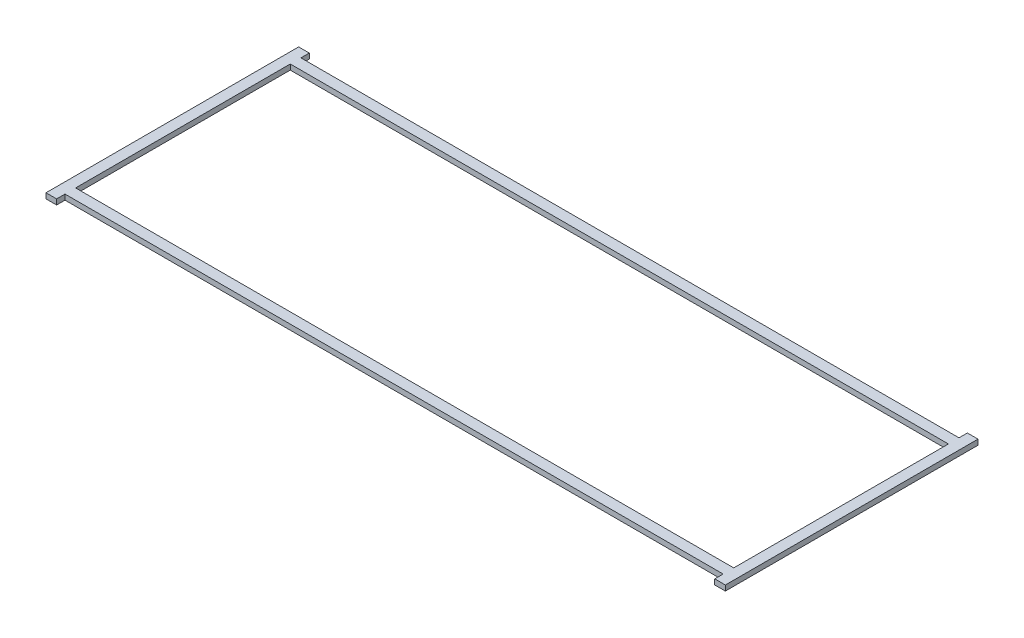
SolidWorks part; units mm, degrees
ref_plane "Front" through (0, 0, 0) normal (0, 0, 1) x (1, 0, 0)
ref_plane "Top" through (0, 0, 0) normal (0, 1, 0) x (1, 0, 0)
ref_plane "Right" through (0, 0, 0) normal (1, 0, 0) x (0, 0, -1)
sketch "Sketch1" plane through (0, 0, 0) normal (0, 1, 0) x (1, 0, 0)
  line L0 (196.85, 75.565) -> (203.2, 75.565)
  line L1 (-203.2, 75.565) -> (-196.85, 75.565)
  line L2 (-203.2, 75.565) -> (-203.2, -75.565)
  line L3 (-203.2, -75.565) -> (-196.85, -75.565)
  line L4 (203.2, 75.565) -> (203.2, -75.565)
  line L5 (-203.2, 75.565) -> (203.2, -75.565) construction
  line L6 (-203.2, -75.565) -> (203.2, 75.565) construction
  line L8 (-196.85, 75.565) -> (-196.85, 70.5549)
  line L9 (-196.85, 70.5549) -> (196.85, 70.5549)
  line L10 (196.85, 75.565) -> (196.85, 70.5549)
  line L12 (-196.85, -75.565) -> (-196.85, -70.5549)
  line L13 (-196.85, -70.5549) -> (196.85, -70.5549)
  line L14 (196.85, -75.565) -> (196.85, -70.5549)
  line L15 (196.85, -75.565) -> (203.2, -75.565)
  line L17 (-196.85, -64.2048) -> (196.85, -64.2048)
  line L18 (-196.85, -64.2048) -> (-196.85, 64.2049)
  line L19 (-196.85, 64.2049) -> (196.85, 64.2049)
  line L20 (196.85, -64.2048) -> (196.85, 64.2049)
  line L21 (-196.85, -64.2048) -> (196.85, 64.2049) construction
  line L22 (-196.85, 64.2049) -> (196.85, -64.2048) construction
  point P0 (0, 0)
  point P14 (0, 0)
  dimension "D1" = 406.4
  dimension "D2" = 151.13
  dimension "D3" = 6.35
  dimension "D4" = 6.35
  dimension "D5" = 141.1097
  dimension "D6" = 6.35
  dimension "D7" = 6.35
extrude "Boss-Extrude1" add sketch "Sketch1" along normal blind 3.175
equation "\"D2@Sketch1\" = 4.87075 + 3 * ( 0.25 + ( 6 / 64 ) + 0.016 )"
equation "\"D5@Sketch1\"= 4.47625 + 3 * ( 0.25 + ( 6 / 64 ) + 0.016 )"
